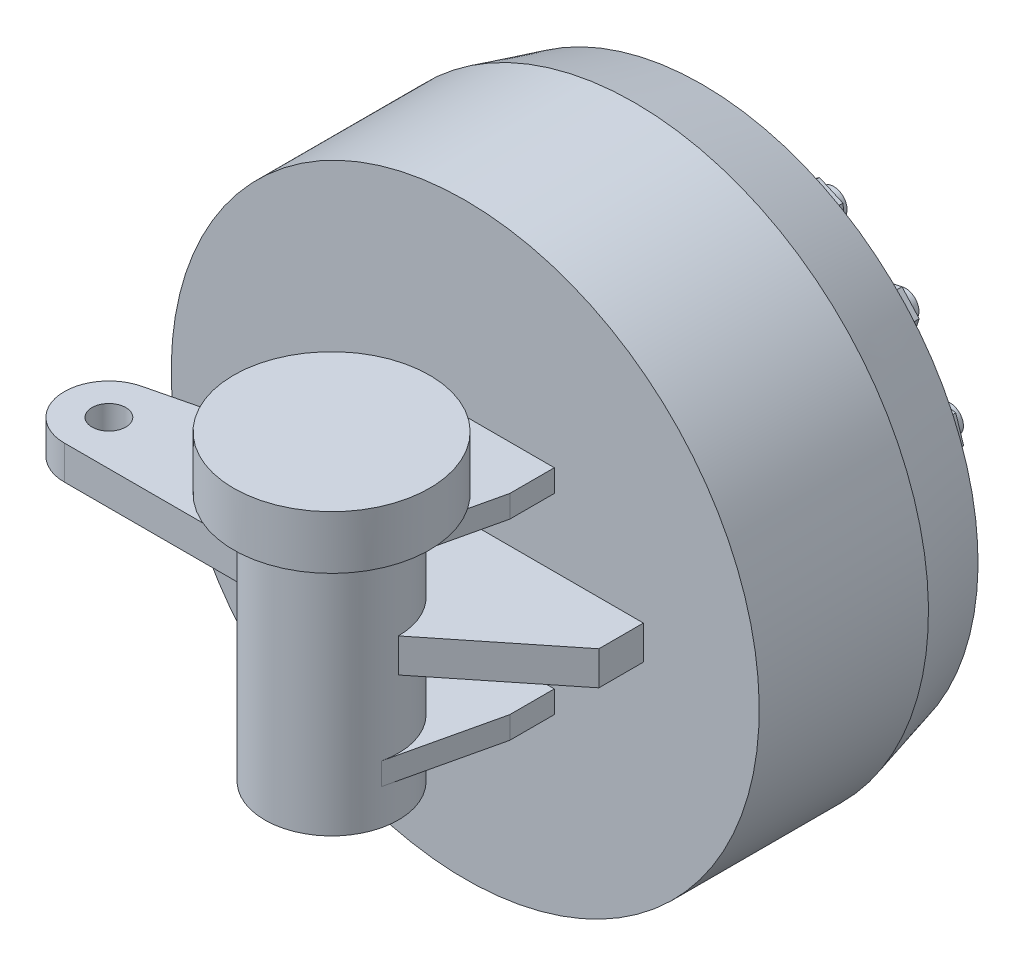
SolidWorks part; units mm, degrees
ref_plane "Front Plane" through (0, 0, 0) normal (0, 0, 1) x (1, 0, 0)
ref_plane "Top Plane" through (0, 0, 0) normal (0, 1, 0) x (1, 0, 0)
ref_plane "Right Plane" through (0, 0, 0) normal (1, 0, 0) x (0, 0, -1)
sketch "Sketch1" plane through (0, 0, 0) normal (1, 0, 0) x (0, 0, -1)
  line L0 (0, 0) -> (0, 165)
  line L1 (0, 165) -> (95, 165)
  line L2 (95, 165) -> (133, 154.8179)
  line L3 (133, 154.8179) -> (133, 75)
  line L4 (133, 75) -> (158, 75)
  line L5 (158, 75) -> (158, 50)
  line L6 (158, 50) -> (183, 50)
  line L7 (183, 50) -> (183, 0)
  line L8 (183, 0) -> (0, 0)
  dimension "D1" = 165
  dimension "D2" = 95
  dimension "D3" = 15
  dimension "D4" = 38
  dimension "D5" = 25
  dimension "D6" = 25
  dimension "D7" = 25
  dimension "D8" = 50
revolve "Revolve1" add sketch "Sketch1" angle 360 about L8
chamfer "Chamfer1" distance 4 angle 45 1 edges at (0, 50, -183)
fillet "Fillet1" radius 3.5 2 edges at (0, 75, -158) (0, 50, -158)
sketch "Sketch2" plane through (0, 0, 0) normal (0, 1, 0) x (1, 0, 0)
  circle A0 centre (0, -75) radius 37.5
  dimension "D2" = 75
  dimension "D1" = 75
extrude "Boss-Extrude1" add sketch "Sketch2" along normal blind 90 and the other way blind 80 separate body
sketch "Sketch3" plane through (0, 0, 0) normal (0, 1, 0) x (1, 0, 0)
  line L0 (0, 0) -> (0, -137.2613) construction
  line L1 (-50, 0) -> (50, 0)
  line L2 (-165, 0) -> (165, 0) construction
  line L3 (50, 0) -> (50, -25)
  line L4 (50, -25) -> (36.543, -83.418)
  line L5 (-50, -25) -> (-36.543, -83.418)
  line L6 (-50, 0) -> (-50, -25)
  line L7 (-36.543, -83.418) -> (36.543, -83.418)
  circle A0 centre (0, -75) radius 37.5 construction
  dimension "D1" = 50
  dimension "D2" = 25
extrude "Boss-Extrude2" add sketch "Sketch3" against normal blind 12.5 from offset 60
mirror "Mirror1" about plane through (0, 0, 0) normal (0, 1, 0) of "Boss-Extrude2"
sketch "Sketch4" plane through (0, 0, 0) normal (0, 1, 0) x (1, 0, 0)
  line L0 (-50, 0) -> (100, 0)
  line L1 (-165, 0) -> (165, 0) construction
  line L2 (100, 0) -> (100, -25)
  line L3 (100, -25) -> (37.5, -75)
  line L4 (0, -75) -> (214.2765, -75) construction
  line L5 (-37.5, -75) -> (-150, -75)
  line L6 (-155.8972, -25.7055) -> (-50, 0)
  circle A0 centre (0, -75) radius 37.5 construction
  arc A1 (36.543, -83.418) -> (-36.543, -83.418) centre (0, -75) ccw construction
  arc A2 (-150, -75) -> (-155.8972, -25.7055) centre (-150, -50) cw
  arc A3 (-37.5, -75) -> (37.5, -75) centre (0, -75) ccw
  circle A4 centre (-150, -50) radius 9.5
  dimension "D1" = 150
  dimension "D5" = 25
  dimension "D6" = 19
  dimension "D2" = 25
  dimension "D3" = 100
  dimension "D4" = 150
extrude "Boss-Extrude3" add sketch "Sketch4" along normal mid plane 19
sketch "Sketch5" plane through (0, 60, 0) normal (0, 1, 0) x (1, 0, 0)
  line L0 (37.5, -75) -> (-37.5, -75) construction
  line L1 (0, 0) -> (0, -112.5) construction
  arc A0 (36.543, -83.418) -> (-36.543, -83.418) centre (0, -75) ccw construction
  circle A1 centre (0, -75) radius 37.5 construction
  circle A2 centre (0, -75) radius 55
  dimension "D1" = 110
extrude "Boss-Extrude4" add sketch "Sketch5" along normal up to surface (30 mm away) up to face at (0, 90, 112.5)
sketch "Sketch6" plane through (0, 0, -133) normal (0, 0, -1) x (-1, 0, 0)
  line L0 (0, -1.3021) -> (0, 169.0221) construction
  line L2 (7.2169, 132.5) -> (-7.2169, 132.5)
  line L3 (-7.2169, 132.5) -> (-14.4338, 120)
  line L4 (-14.4338, 120) -> (-7.2169, 107.5)
  line L5 (-7.2169, 107.5) -> (7.2169, 107.5)
  line L6 (7.2169, 107.5) -> (14.4338, 120)
  line L7 (14.4338, 120) -> (7.2169, 132.5)
  circle A0 centre (0, 120) radius 12.5 construction
  circle A1 centre (0, 120) radius 7.5
  dimension "D3" = 15
  dimension "D1" = 25
  dimension "D2" = 120
extrude "Boss-Extrude5" add sketch "Sketch6" along normal blind 25 contours A1 region at (0, 120, -133)
extrude "Boss-Extrude6" add sketch "Sketch6<3>" along normal blind 12.5 from offset 6
sketch "Sketch6<3>" plane through (0, 0, -133) normal (0, 0, -1) x (-1, 0, 0) same geometry as "Sketch6"
pattern_circular "CirPattern2" count 15 over 360 about axis through (0, 0, -183) along (0, 0, -1) of "Boss-Extrude6", "Boss-Extrude5"
